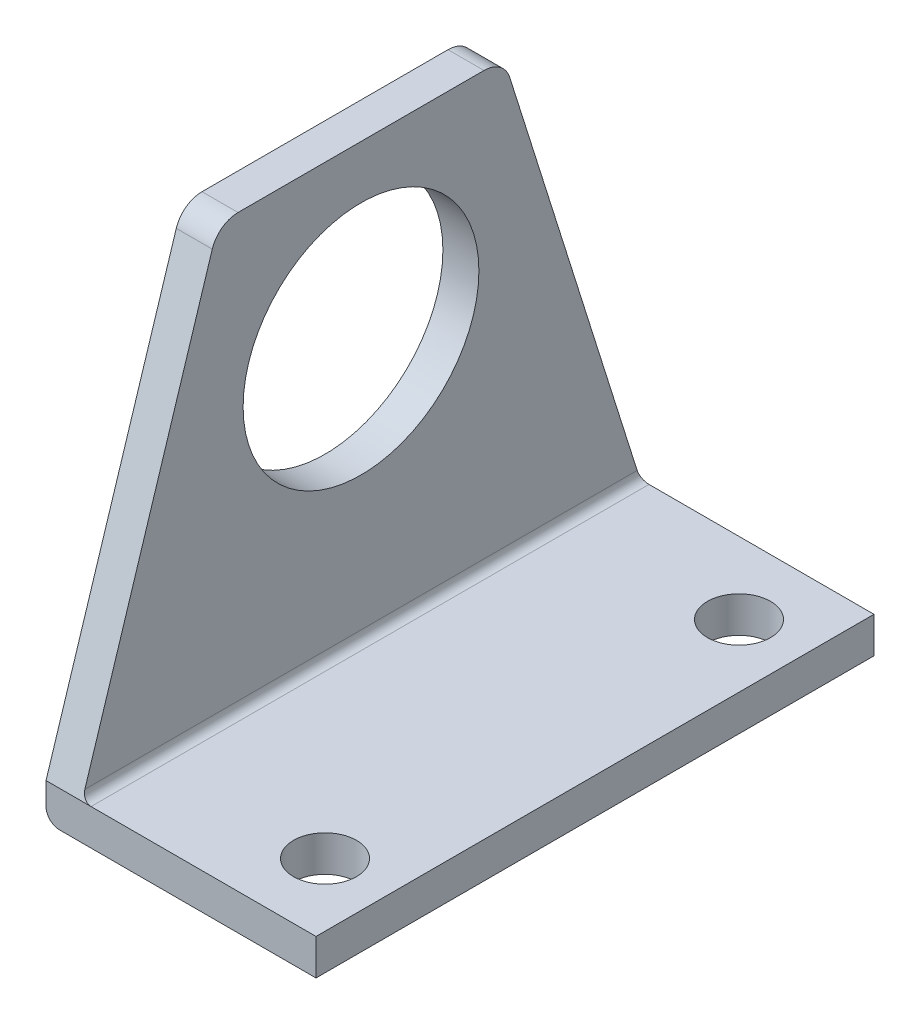
SolidWorks part; units mm, degrees
ref_plane "前视基准面" through (0, 0, 0) normal (0, 0, 1) x (1, 0, 0)
ref_plane "上视基准面" through (0, 0, 0) normal (0, 1, 0) x (1, 0, 0)
ref_plane "右视基准面" through (0, 0, 0) normal (1, 0, 0) x (0, 0, -1)
sketch "草图1" plane through (0, 0, 0) normal (1, 0, 0) x (0, 0, -1)
  line L0 (-31, 0) -> (31, 0)
  line L1 (31, 0) -> (31, 4)
  line L2 (31, 4) -> (16.5271, 49.9021)
  line L3 (13.666, 52) -> (-13.666, 52)
  line L4 (-16.5271, 49.9021) -> (-31, 4)
  line L5 (-31, 4) -> (-31, 0)
  arc A0 (16.5271, 49.9021) -> (13.666, 52) centre (13.666, 49) ccw
  arc A1 (-13.666, 52) -> (-16.5271, 49.9021) centre (-13.666, 49) ccw
  circle A2 centre (0, 33) radius 13.1
extrude "凸台-拉伸1" add sketch "草图1" along normal blind 30
sketch "草图2" plane through (0, 0, 0) normal (0, 0, 1) x (1, 0, 0)
  line L0 (5, 4) -> (30, 4)
  line L1 (30, 4) -> (30, 52)
  line L2 (30, 52) -> (4, 52)
  line L3 (4, 52) -> (4, 5)
  arc A0 (4, 5) -> (5, 4) centre (5, 5) ccw
extrude "切除-拉伸1" cut sketch "草图2" along normal blind 31 and the other way blind 31
sketch "草图3" plane through (0, 0, 0) normal (0, 0, 1) x (1, 0, 0)
  line L0 (-1, -1) -> (1.5, -1)
  line L1 (1.5, -1) -> (1.5, 0)
  line L2 (0, 1.5) -> (-1, 1.5)
  line L3 (-1, 1.5) -> (-1, -1)
  arc A0 (1.5, 0) -> (0, 1.5) centre (1.5, 1.5) cw
extrude "切除-拉伸2" cut sketch "草图3" along normal blind 31 and the other way blind 31
sketch "草图4" plane through (0, 0, 0) normal (0, 1, 0) x (1, 0, 0)
  circle A0 centre (23, 23) radius 3.5
extrude "切除-拉伸3" cut sketch "草图4" along normal blind 4 and the other way blind 4
sketch "草图5" plane through (0, 0, 0) normal (0, 1, 0) x (1, 0, 0)
  circle A0 centre (23, -23) radius 3.5
extrude "切除-拉伸4" cut sketch "草图5" along normal blind 4 and the other way blind 4
ref_plane "基准面1" through (4, 0, 0) normal (1, 0, 0) x (0, 0, -1)
ref_plane "For Nut XY" through (4, 0, 0) normal (1, 0, 0) x (0, 0, -1)
ref_plane "For Nut XZ" through (0, 33, 0) normal (0, -1, 0) x (-1, 0, 0)
ref_plane "For Nut YZ" through (0, 0, 0) normal (0, 0, -1) x (-1, 0, 0)
ref_axis "For Nut X" through (4, 33, 80.9) along (0, 0, -1)
ref_axis "For Nut Y" through (4, -50, 0) along (0, 1, 0)
ref_axis "For Nut Z" through (80.9, 33, 0) along (-1, 0, 0)
sketch3d "For Nut"
  point P0 (4, 33, 0)
ref_plane "For front cover XY" through (0, 0, 0) normal (-1, 0, 0) x (0, 0, 1)
ref_plane "For front cover XZ" through (0, 33, 0) normal (0, 1, 0) x (1, 0, 0)
ref_plane "For front cover YZ" through (0, 0, 0) normal (0, 0, -1) x (-1, 0, 0)
ref_axis "For front cover X" through (0, 33, 80.9) along (0, 0, -1)
ref_axis "For front cover Y" through (0, 50, 0) along (0, -1, 0)
ref_axis "For front cover Z" through (-80.9, 33, 0) along (1, 0, 0)
sketch3d "For front cover"
  point P0 (0, 33, 0)
